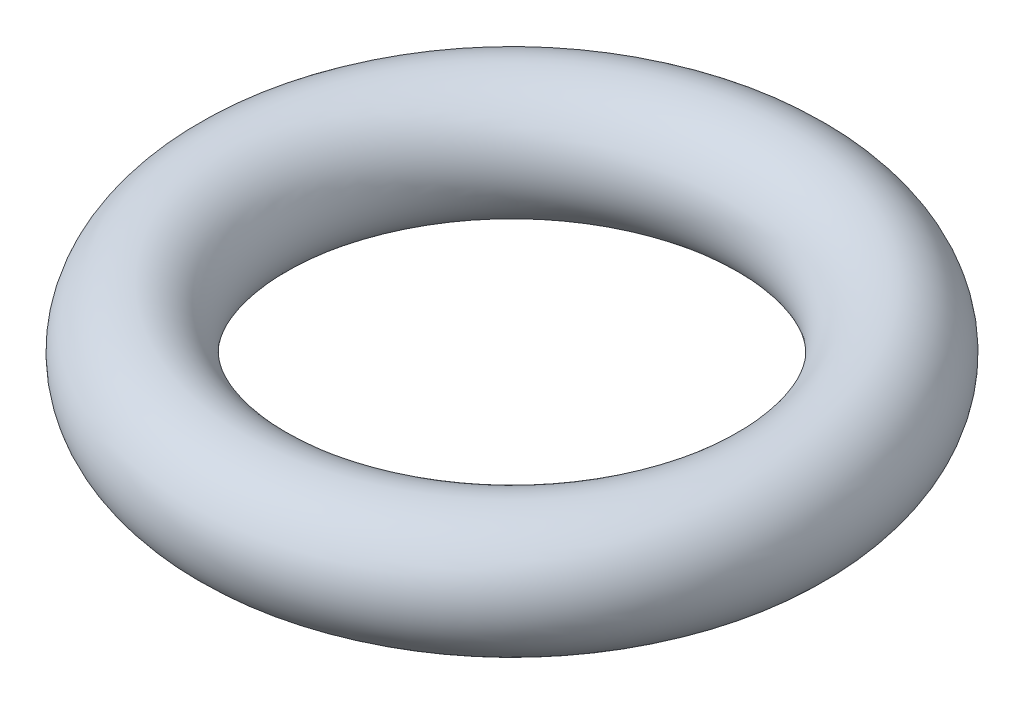
SolidWorks part; units mm, degrees
ref_plane "Alzado" through (0, 0, 0) normal (0, 0, 1) x (1, 0, 0)
ref_plane "Planta" through (0, 0, 0) normal (0, 1, 0) x (1, 0, 0)
ref_plane "Vista lateral" through (0, 0, 0) normal (1, 0, 0) x (0, 0, -1)
sketch "Croquis1" plane through (0, 0, 0) normal (1, 0, 0) x (0, 0, -1)
  line L0 (-3.925, 6.8126) -> (-3.925, -6.8635) construction
  circle A0 centre (0, 0) radius 0.89
  dimension "D1" = 1.78
  dimension "D2" = 3.925
revolve "Revolución1" add sketch "Croquis1" angle 360 about L0
sketch "Croquis2" plane through (0, 0, 0) normal (1, 0, 0) x (0, 0, -1)
  line L0 (-3.925, 4.1153) -> (-3.925, -3.7377) construction
  dimension "D1" = 3.925
ref_plane "Plane1" through (0, 0, 3.93) normal (0, 0, 1) x (1, 0, 0)
ref_axis "Axis1" through (0, 0.979, 3.93) along (0, -1, 0)
ref_plane "Plane2" through (0, 0.89, 0) normal (0, 1, 0) x (1, 0, 0)
